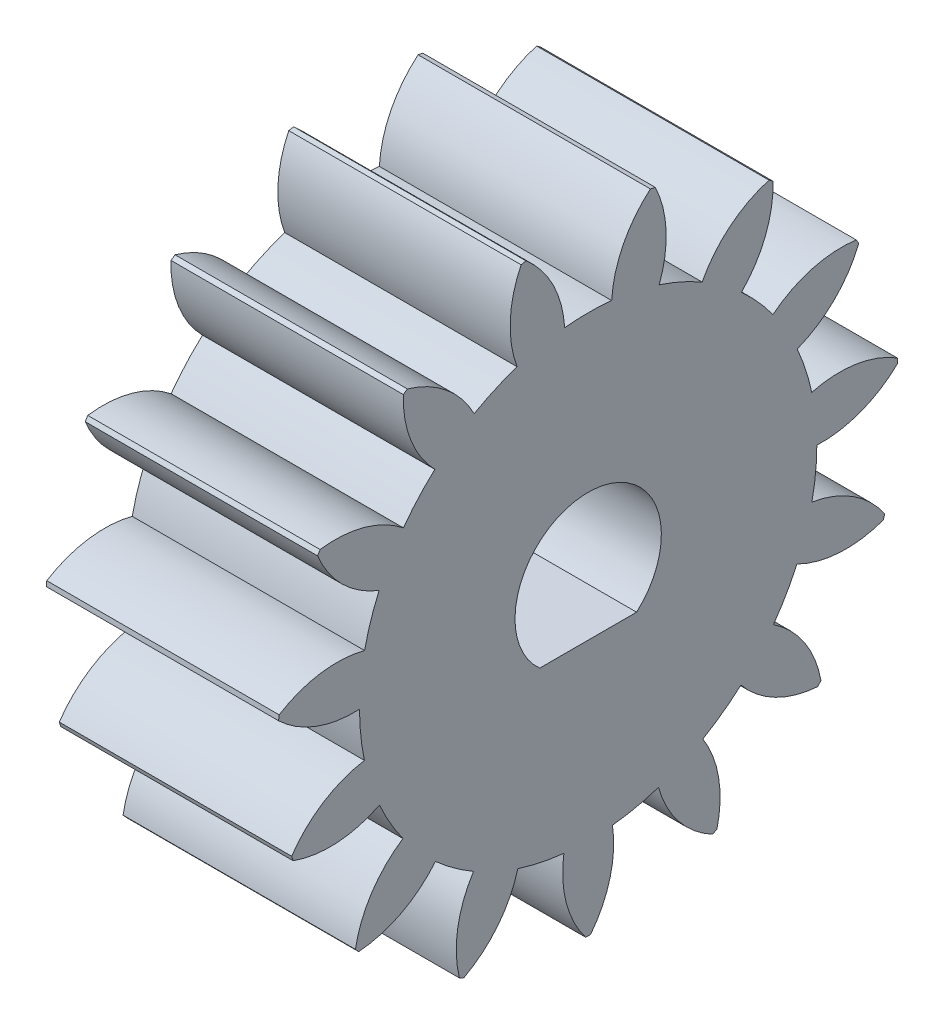
SolidWorks part; units mm, degrees
ref_plane "Plane1" through (0, 0, 0) normal (0, 0, 1) x (1, 0, 0)
ref_plane "Plane2" through (0, 0, 0) normal (0, 1, 0) x (1, 0, 0)
ref_plane "Plane3" through (0, 0, 0) normal (1, 0, 0) x (0, 0, -1)
sketch "HoldingSke" plane through (0, 0, 0) normal (0, 1, 0) x (1, 0, 0)
  line L0 (0, 0) -> (0.483, -0.1294)
  line L1 (-15, 0) -> (100, 0) construction
  line L2 (0, 0) -> (-2.1039, 2.3779)
  line L3 (0, 0) -> (-11.863, 4.5341)
  line L4 (0, 0) -> (8.3417, 2.2352)
  line L5 (0, 0) -> (-23.7986, -8.8762)
  line L6 (0, 0) -> (-10.5278, -7.1032)
  line L7 (-2.1039, 2.3779) -> (3.3635, 27.1828)
  line L8 (-76.2, 54.61) -> (-73.66, 54.61)
  line L9 (-71.009, 38.7566) -> (-53.1078, 45.2721)
  line L10 (-76.2, 71.12) -> (104.1128, 71.12)
  line L11 (0, 0) -> (-12.7, 0)
  line L12 (-76.2, 101.6) -> (-75.9714, 101.6)
  line L13 (24.9733, 27.94) -> (52.9518, 28.4284)
  line L14 (24.9733, 27.94) -> (24.9746, 27.94)
  line L15 (24.9733, 27.94) -> (100.4006, 29.5858)
  line L16 (-63.627, -2) -> (-12.827, -2)
  circle A0 centre (0, 0) radius 4
  circle A1 centre (0, 0) radius 9.4987
  circle A2 centre (0, 0) radius 12.7
  circle A3 centre (0, 0) radius 4
  dimension "Num_teeth" = 15
  dimension "Pitch_radius" = 180.3128
  dimension "Width" = 12.7
  dimension "Thickness" = 12.7
sketch "BasProSke" plane through (0, 0, 0) normal (0, 1, 0) x (1, 0, 0)
  line L0 (-10, 0) -> (60, 0) construction
  line L1 (0, 0) -> (0, 17)
  line L2 (0, 0) -> (12.7, 0)
  line L3 (12.7, 0) -> (12.7, 17)
  line L4 (12.7, 17) -> (0, 17)
  dimension "Thickness" = 12.7
  dimension "Diameter" = 34
revolve "Base-Revolve" add sketch "BasProSke" angle 360 about L0
sketch "TooCutSke" plane through (0, 0, 0) normal (1, 0, 0) x (0, 0, -1)
  line L1 (0, 0) -> (0, 107) construction
  line L2 (0, 0) -> (-1.9669, 14.8705) construction
  line L3 (0, 0) -> (-6.2184, 29.2554) construction
  line L4 (-1.9669, 14.8705) -> (-3.1092, 14.6277) construction
  arc A0 (1.2856, 12.4324) -> (-1.2856, 12.4324) centre (0, 0) ccw
  arc A1 (3.4272, 16.6769) -> (-3.4272, 16.6769) centre (0, 0) ccw
  circle A2 centre (0, 0) radius 15 construction
  circle A3 centre (0, 0) radius 14.0954 construction
  arc A4 (-1.2856, 12.4324) -> (-3.4272, 16.6769) centre (-7.2748, 12.073) ccw
  arc A5 (3.4272, 16.6769) -> (1.2856, 12.4324) centre (7.2748, 12.073) ccw
extrude "ToothCut" cut sketch "TooCutSke" along normal through all
fillet "Breaks" [suppressed] radius 0.04 tangent propagation no
fillet "RootFillets" [suppressed] radius 0.5013
pattern_circular "TeethCuts" count 15 every 24 about axis through (-10, 0, 0) along (1, 0, 0) of "ToothCut", "RootFillets", "Breaks"
sketch "HubNeaOneSke" plane through (0, 0, 0) normal (-1, 0, 0) x (0, 0, 1)
  circle A0 centre (0, 0) radius 9.4987
  dimension "Diameter" = 18.9975
extrude "HubNearOne" [suppressed] add sketch "HubNeaOneSke" along normal blind 12.7004
sketch "HubNeaBotSke" plane through (0, 0, 0) normal (-1, 0, 0) x (0, 0, 1)
  circle A0 centre (0, 0) radius 9.4987
  dimension "Diameter" = 18.9975
extrude "HubNearBoth" [suppressed] add sketch "HubNeaBotSke" along normal blind 6.3502
ref_plane "FarPln" through (12.7, 0, 0) normal (1, 0, 0) x (0, 0, -1)
sketch "HubFarSke" plane through (12.7, 0, 0) normal (1, 0, 0) x (0, 0, -1)
  circle A0 centre (0, 0) radius 9.4987
  dimension "Diameter" = 18.9975
extrude "HubFar" [suppressed] add sketch "HubFarSke" along normal blind 6.3502
sketch "BorSke" plane through (0, 0, 0) normal (1, 0, 0) x (0, 0, -1)
  circle A0 centre (0, 0) radius 4
  dimension "Diameter" = 8
extrude "Bore" cut sketch "BorSke" along normal mid plane 50.8007
sketch "KeySke" plane through (0, 0, 0) normal (1, 0, 0) x (0, 0, -1)
  line L0 (-3.175, 0) -> (-3.175, 6.54)
  line L1 (-3.175, 6.54) -> (3.175, 6.54)
  line L2 (3.175, 6.54) -> (3.175, 0)
  line L3 (0, 0) -> (0, 34) construction
  line L4 (-3.175, 0) -> (3.175, 0)
  dimension "Width" = 6.35
extrude "Keyway" [suppressed] cut sketch "KeySke" along normal mid plane 50.8007
pattern_circular "Keyway2" [suppressed] count 2 every 90 about axis through (-10, 0, 0) along (1, 0, 0) reverse direction yes
sketch "Szkic1" [suppressed] plane through (0, 0, 0) normal (1, 0, 0) x (0, 0, -1)
  line L0 (4, -5.8283) -> (4, 7.2616) construction
  line L2 (-7.7998, -4.1403) -> (-7.7998, 4.4855)
  line L3 (-7.7998, -4.1403) -> (-3, -4.1403)
  line L4 (-7.7998, 4.4855) -> (-3, 4.4855)
  line L5 (-3, -4.1403) -> (-3, 4.4855)
  circle A0 centre (0, 0) radius 4 construction
  dimension "D1" = 7
extrude "Dodanie-wyciągnięcie1" [suppressed] add sketch "Szkic1" along normal blind 9
sketch "Szkic2" plane through (0, 0, 0) normal (1, 0, 0) x (0, 0, -1)
  line L1 (-2.6458, -4) -> (2.6458, -4)
  line L2 (-2.6458, -4) -> (-2.6458, -3)
  line L3 (-2.6458, -3) -> (2.6458, -3)
  line L4 (2.6458, -4) -> (2.6458, -3)
  circle A0 centre (0, 0) radius 4 construction
  dimension "D1" = 1
extrude "Dodanie-wyciągnięcie2" add sketch "Szkic2" along normal up to surface (12.7 mm away) up to face at (12.7, 0, 4)
equation "' \"Module@HoldingSke\" = 6.35"
equation "' \"Num_teeth@HoldingSke\" = 12"
equation "' \"Ap@HoldingSke\" =  20"
equation "' \"Ap@HoldingSke\" = 20"
equation "' \"Width@HoldingSke\" = 0.5 * 25.4"
equation "' \"Hub_dia@HoldingSke\"= 1 * 25.4"
equation "' \"Hub_dia@HoldingSke\" = 1 * 25.4"
equation "' \"Overall_len@HoldingSke\" = 1.0 * 25.4"
equation "' \"Bore@HoldingSke\" = 0.75 * 25.4"
equation "' \"T_dim@HoldingSke\" = 0.1 * 25.4"
equation "' \"Width@KeySke\" = 0.25 * 25.4"
equation "' \"Show_teeth@HoldingSke\" = 13"
equation "' \"Backlash@HoldingSke\" = 0.009 * 25.4"
equation "' \"Addendum_fac@HoldingSke\" = 1.0"
equation "' \"Dedendum_fac@HoldingSke\" = 1.25"
equation "' \"Dedendum_add@HoldingSke\" = 0.00005 * 25.4"
equation "' \"Clearance_fac@HoldingSke\" = 0.25"
equation "\"Pitch@HoldingSke\"= 1 / \"Module@HoldingSke\""
equation "\"Overcut_dia@TooCutSke\" = (\"Num_teeth@HoldingSke\" + 2 * \"Addendum_fac@HoldingSke\") / \"Pitch@HoldingSke\" + 0.002 * 25.4"
equation "\"Pitch_dia@TooCutSke\" = \"Num_teeth@HoldingSke\" / \"Pitch@HoldingSke\""
equation "\"Base_dia@TooCutSke\" = \"Num_teeth@HoldingSke\" / \"Pitch@HoldingSke\" * cos((\"Ap@HoldingSke\"  * 3.14159265 / 180))"
equation "\"Root_dia@TooCutSke\" = (\"Num_teeth@HoldingSke\" + 2) / \"Pitch@HoldingSke\" - 2 * (\"Addendum_fac@HoldingSke\" + \"Dedendum_fac@HoldingSke\") / \"Pitch@HoldingSke\" - \"Dedendum_add@HoldingSke\" * 2"
equation "\"Half_ang@TooCutSke\" = 180 / \"Num_teeth@HoldingSke\""
equation "\"Half_CT@TooCutSke\" = \"Num_teeth@HoldingSke\" / \"Pitch@HoldingSke\" * sin((3.14159265 / 2 / \"Num_teeth@HoldingSke\")) / 2 - 7 * \"Backlash@HoldingSke\" / 4"
equation "\"Flank_rad@TooCutSke\" = \"Num_teeth@HoldingSke\" / \"Pitch@HoldingSke\" / 5"
equation "\"Radius@RootFillets\" = \"Clearance_fac@HoldingSke\" / \"Pitch@HoldingSke\" + \"Dedendum_add@HoldingSke\""
equation "\"Break_rad@Breaks\" = 0.02 / \"Pitch@HoldingSke\""
equation "\"Thickness@HoldingSke\"= \"Width@HoldingSke\""
equation "\"OAL@HoldingSke\" = \"Thickness@HoldingSke\""
equation "\"MHD@HoldingSke\" = (\"Num_teeth@HoldingSke\" + 2) / \"Pitch@HoldingSke\" - 2 * (\"Addendum_fac@HoldingSke\" + \"Dedendum_fac@HoldingSke\")  / \"Pitch@HoldingSke\" - \"Dedendum_add@HoldingSke\" * 2"
equation "\"MBD@HoldingSke\" = (\"Num_teeth@HoldingSke\" + 2) / \"Pitch@HoldingSke\" - 2 * (\"Addendum_fac@HoldingSke\" + \"Dedendum_fac@HoldingSke\")  / \"Pitch@HoldingSke\" - \"Dedendum_add@HoldingSke\" * 2 - 0.002 * 25.4"
equation "\"MHD@HoldingSke\" = ((sgn( \"MHD@HoldingSke\" - \"Hub_dia@HoldingSke\" )-1)*( \"MHD@HoldingSke\" - \"Hub_dia@HoldingSke\" ))/-2+ \"Hub_dia@HoldingSke\""
equation "\"MBD@HoldingSke\" = ((sgn( \"MBD@HoldingSke\" - \"Bore@HoldingSke\" )-1)*( \"MBD@HoldingSke\" - \"Bore@HoldingSke\" ))/-2+ \"Bore@HoldingSke\""
equation "\"OAL@HoldingSke\" = ((sgn( \"OAL@HoldingSke\" - \"Overall_len@HoldingSke\" )+1)*( \"OAL@HoldingSke\" - \"Overall_len@HoldingSke\" ))/2 + \"Overall_len@HoldingSke\" + 0.000002 * 25.4"
equation "\"Num_teeth@TeethCuts\" = int( \"Show_teeth@HoldingSke\" ) + 1"
equation "\"Num_teeth@TeethCuts\" = ((sgn( \"Num_teeth@TeethCuts\" - \"Num_teeth@HoldingSke\" )-1)*( \"Num_teeth@TeethCuts\" - \"Num_teeth@HoldingSke\" ))/-2+ \"Num_teeth@HoldingSke\""
equation "\"Num_teeth@TeethCuts\"= ( ( sgn ( \"Num_teeth@TeethCuts\" - 2.0 ) + 1 ) * ( \"Num_teeth@TeethCuts\" - 2.0 ) ) / 2 + 2.0"
equation "\"Angle@TeethCuts\" = 360.0 / \"Num_teeth@HoldingSke\""
equation "\"Diameter@BasProSke\" = (\"Num_teeth@HoldingSke\" + 2 * \"Addendum_fac@HoldingSke\") / \"Pitch@HoldingSke\""
equation "\"Thickness@BasProSke\"  = \"Thickness@HoldingSke\""
equation "' \"Fillet_rad@BasProSke\" =  \"Thickness@HoldingSke\" * 0.05"
equation "' \"Fillet_rad@BasProSke\" = \"Thickness@HoldingSke\" * 0.05"
equation "\"MHD@HoldingSke\" = ((sgn( \"MHD@HoldingSke\" - \"Root_dia@TooCutSke\" )-1)*( \"MHD@HoldingSke\" - \"Root_dia@TooCutSke\" ))/-2+ \"Root_dia@TooCutSke\""
equation "\"Diameter@HubNeaOneSke\" = \"MHD@HoldingSke\""
equation "\"Length@HubNearOne\" = \"OAL@HoldingSke\" - \"Thickness@BasProSke\""
equation "\"Diameter@HubNeaBotSke\" = \"MHD@HoldingSke\""
equation "\"Length@HubNearBoth\" = ( \"OAL@HoldingSke\" - \"Thickness@BasProSke\" ) / 2.0"
equation "\"Thickness@FarPln\" = \"Thickness@BasProSke\""
equation "\"Diameter@HubFarSke\" = \"MHD@HoldingSke\""
equation "\"Length@HubFar\" = ( \"OAL@HoldingSke\" - \"Thickness@BasProSke\" ) / 2.0"
equation "\"Diameter@BorSke\" = \"MBD@HoldingSke\""
equation "\"D1@Bore\" = \"OAL@HoldingSke\" * 2.0"
equation "\"D1@Keyway\" = \"OAL@HoldingSke\" * 2.0"
equation "\"Offset@KeySke\" = \"T_dim@HoldingSke\" + \"MBD@HoldingSke\" / 2.0"
